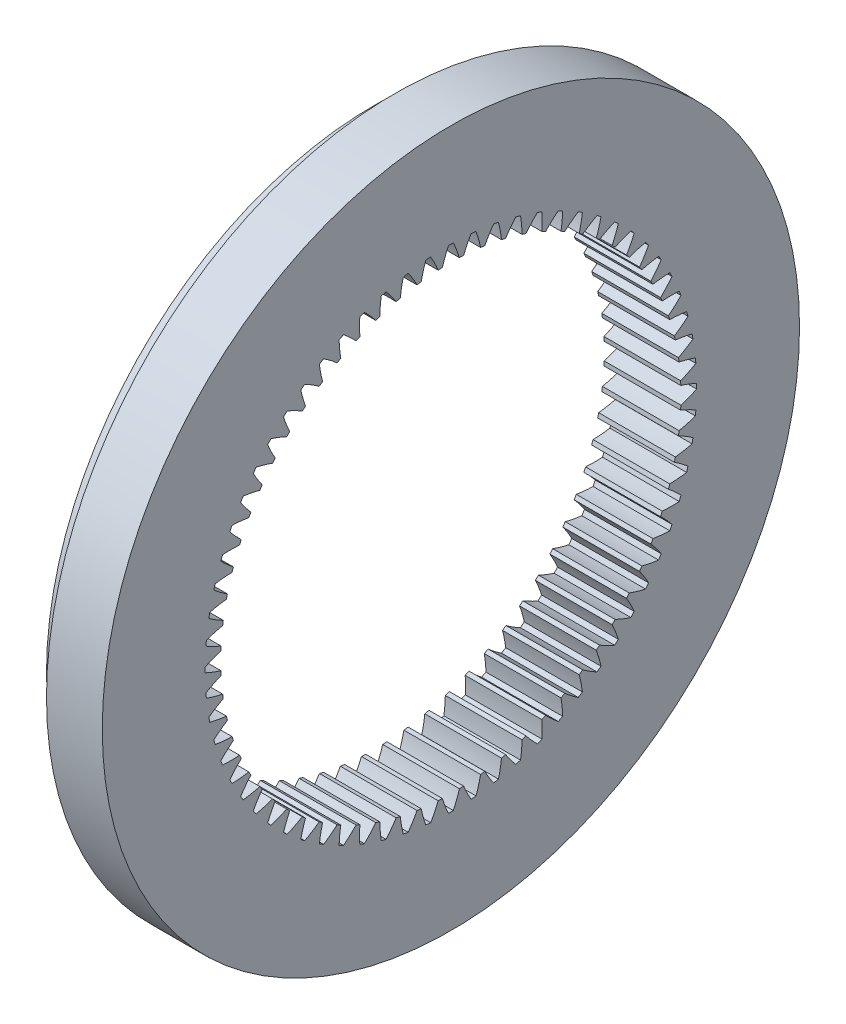
SolidWorks part; units mm, degrees
ref_plane "Plane1" through (0, 0, 0) normal (0, 0, 1) x (1, 0, 0)
ref_plane "Plane2" through (0, 0, 0) normal (0, 1, 0) x (1, 0, 0)
ref_plane "Plane3" through (0, 0, 0) normal (1, 0, 0) x (0, 0, -1)
sketch "HoldingSke" plane through (0, 0, 0) normal (0, 1, 0) x (1, 0, 0)
  line L0 (0, 0) -> (0.3746, -0.9272)
  line L1 (-15, 0) -> (100, 0) construction
  line L2 (0, 0) -> (-2.1039, 2.3779)
  line L3 (0, 0) -> (-11.863, 4.5341)
  line L4 (0, 0) -> (3.2351, 8.0072)
  line L5 (0, 0) -> (-23.7986, -8.8762)
  line L6 (0, 0) -> (-10.5278, -7.1032)
  line L7 (-2.1039, 2.3779) -> (3.3635, 27.1825)
  line L8 (-76.2, 3.3779) -> (-54.61, 3.3779)
  line L9 (-71.009, 38.7566) -> (-53.1078, 45.2721)
  line L10 (-76.2, 71.12) -> (104.1128, 71.12)
  line L11 (0, 0) -> (-11, 0)
  line L12 (-76.2, 101.6) -> (-76.162, 101.6)
  line L13 (24.9733, 27.94) -> (52.9518, 28.4284)
  line L14 (24.9733, 27.94) -> (24.9743, 27.94)
  line L15 (24.9733, 27.94) -> (100.4006, 29.5858)
  circle A0 centre (0, 0) radius 47
  circle A1 centre (0, 0) radius 12.7
  circle A2 centre (0, 0) radius 12.7
  dimension "Num_teeth" = 68
  dimension "Pitch_radius" = 180.3128
  dimension "Width" = 11
  dimension "Diameter" = 94
sketch "BasProSke" plane through (0, 0, 0) normal (0, 1, 0) x (1, 0, 0)
  line L0 (-10, 0) -> (60, 0) construction
  line L1 (0, 33) -> (0, 47)
  line L2 (0, 33) -> (11, 33)
  line L3 (11, 33) -> (11, 47)
  line L4 (11, 47) -> (0, 47)
  dimension "Thickness" = 11
  dimension "Diameter" = 94
revolve "Base-Revolve" add sketch "BasProSke" angle 360 about L0
sketch "TooCutSke" plane through (0, 0, 0) normal (1, 0, 0) x (0, 0, -1)
  line L3 (0.8803, 33.9886) -> (0.8803, 53.6633) construction
  line L4 (0, 0) -> (0, 59.563) construction
  line L5 (0, 0) -> (-3.1556, 68.2546) construction
  line L6 (-15.0631, 28.0889) -> (36.4744, 30.4716) construction
  circle A0 centre (0, 0) radius 34 construction
  circle A1 centre (0, 0) radius 35.251 construction
  circle A2 centre (0, 0) radius 28.7546 construction
  circle A3 centre (0, 0) radius 32.9746 construction
  arc A4 (1.2265, 32.9518) -> (0.3554, 35.2492) centre (-15.0631, 28.0889) ccw
  arc A5 (1.2265, 32.9518) -> (-1.2265, 32.9518) centre (0, 0) ccw
  arc A6 (0.3554, 35.2492) -> (-0.3554, 35.2492) centre (0, 0) ccw
  arc A7 (-0.3554, 35.2492) -> (-1.2265, 32.9518) centre (15.0631, 28.0889) ccw
extrude "ToothCut" cut sketch "TooCutSke" along normal through all
fillet "Breaks" [suppressed] radius 0.1
fillet "RootFillets" [suppressed] radius 0.251
pattern_circular "TeethCuts" count 68 every 5.294 about axis through (-10, 0, 0) along (1, 0, 0) of "RootFillets", "Breaks", "ToothCut"
sketch "Sketch1" plane through (11, 0, 0) normal (1, 0, 0) x (0, 0, -1)
  circle A0 centre (0, 0) radius 50
  circle A1 centre (0, 0) radius 47 construction
  circle A2 centre (0, 0) radius 47
  point P2 (0, 0)
  dimension "D1" = 100
extrude "Boss-Extrude1" add sketch "Sketch1" against normal blind 8
equation "' \"Module@HoldingSke\" = 6.35"
equation "' \"Num_teeth@HoldingSke\" = 24"
equation "' \"Ap@HoldingSke\" =  14.5"
equation "' \"Ap@HoldingSke\" = 14.5"
equation "' \"Width@HoldingSke\" = 12"
equation "' \"Diameter@HoldingSke\" = 8 * 25.4"
equation "' \"Show_teeth@HoldingSke\" = 100"
equation "' \"Backlash@HoldingSke\" = 0.009 * 25.4"
equation "' \"Addendum_fac@HoldingSke\" = 1.0"
equation "' \"Dedendum_fac@HoldingSke\" = 1.25"
equation "' \"Dedendum_add@HoldingSke\" = 0.00005 * 25.4"
equation "' \"Clearance_fac@HoldingSke\" = 0.25"
equation "\"Pitch@HoldingSke\" = 1 / \"Module@HoldingSke\" "
equation "\"Overcut_dia@TooCutSke\" = (\"Num_teeth@HoldingSke\" - 2 * \"Addendum_fac@HoldingSke\") / \"Pitch@HoldingSke\" - 0.002 * 25.4"
equation "\"Pitch_dia@TooCutSke\" = \"Num_teeth@HoldingSke\" / \"Pitch@HoldingSke\""
equation "\"Base_dia@TooCutSke\" = \"Num_teeth@HoldingSke\" / \"Pitch@HoldingSke\" * cos((\"Ap@HoldingSke\"  * 3.14159265 / 180)) * 0.90"
equation "\"Root_dia@TooCutSke\" = \"Num_teeth@HoldingSke\"  / \"Pitch@HoldingSke\" + 2 *  \"Dedendum_fac@HoldingSke\"/ \"Pitch@HoldingSke\" + \"Dedendum_add@HoldingSke\" * 2"
equation "\"Half_ang@TooCutSke\" = 180 / \"Num_teeth@HoldingSke\""
equation "\"Half_CT@TooCutSke\" = \"Num_teeth@HoldingSke\" / \"Pitch@HoldingSke\" * sin((3.14159265 / 2 / \"Num_teeth@HoldingSke\")) / 2 + 10 * \"Backlash@HoldingSke\" / 4"
equation "\"Flank_rad@TooCutSke\" = \"Num_teeth@HoldingSke\" / \"Pitch@HoldingSke\" / 4"
equation "\"Radius@RootFillets\"= \"Clearance_fac@HoldingSke\" / \"Pitch@HoldingSke\" + \"Dedendum_add@HoldingSke\""
equation "\"Break_rad@Breaks\" = 0.02 / \"Pitch@HoldingSke\" * 5"
equation "\"Num_teeth@TeethCuts\" = int( \"Show_teeth@HoldingSke\" ) + 1"
equation "\"Num_teeth@TeethCuts\" = ((sgn( \"Num_teeth@TeethCuts\" - \"Num_teeth@HoldingSke\" )-1)*( \"Num_teeth@TeethCuts\" - \"Num_teeth@HoldingSke\" ))/-2+ \"Num_teeth@HoldingSke\""
equation "\"Num_teeth@TeethCuts\" = ((sgn( \"Num_teeth@TeethCuts\" - 2.0)+1)*( \"Num_teeth@TeethCuts\" - 2.0))/2 +2.0"
equation "\"Angle@TeethCuts\" = 360.0 / \"Num_teeth@HoldingSke\""
equation "\"Diameter@BasProSke\" = \"Num_teeth@HoldingSke\"  / \"Pitch@HoldingSke\" + 2 *  \"Dedendum_fac@HoldingSke\"/ \"Pitch@HoldingSke\" + \"Dedendum_add@HoldingSke\" * 2 + 0.002 * 25.4"
equation "\"Diameter@BasProSke\" = ((sgn( \"Diameter@BasProSke\"  - \"Diameter@HoldingSke\" )+1)*( \"Diameter@BasProSke\"  - \"Diameter@HoldingSke\" ))/2 + \"Diameter@HoldingSke\""
equation "\"Inside_diameter@BasProSke\" =  (\"Num_teeth@HoldingSke\" - 2 * \"Addendum_fac@HoldingSke\") / \"Pitch@HoldingSke\" "
equation "\"Thickness@BasProSke\"  = \"Width@HoldingSke\""
